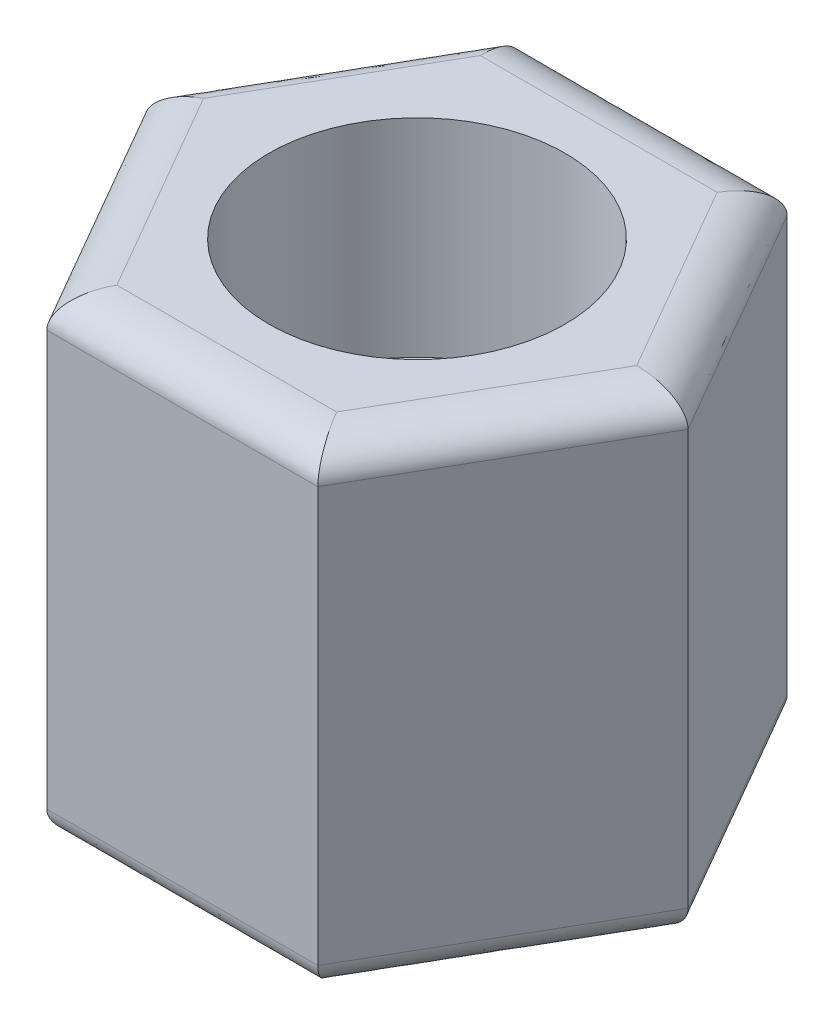
SolidWorks part; units mm, degrees
ref_plane "Front Plane" through (0, 0, 0) normal (0, 0, 1) x (1, 0, 0)
ref_plane "Top Plane" through (0, 0, 0) normal (0, 1, 0) x (1, 0, 0)
ref_plane "Right Plane" through (0, 0, 0) normal (1, 0, 0) x (0, 0, -1)
sketch "Sketch1" plane through (0, 0, 0) normal (0, 1, 0) x (1, 0, 0)
  line L1 (18.3, 0) -> (9.15, 15.8483)
  line L2 (9.15, 15.8483) -> (-9.15, 15.8483)
  line L3 (-9.15, 15.8483) -> (-18.3, 0)
  line L4 (-18.3, 0) -> (-9.15, -15.8483)
  line L5 (-9.15, -15.8483) -> (9.15, -15.8483)
  line L6 (9.15, -15.8483) -> (18.3, 0)
  circle A0 centre (0, 0) radius 18.3 construction
extrude "Boss-Extrude1" add sketch "Sketch1" along normal blind 32
sketch "Sketch2" plane through (0, 32, 0) normal (0, 1, 0) x (1, 0, 0)
  circle A0 centre (0, 0) radius 10
  dimension "D1" = 20
extrude "Cut-Extrude1" cut sketch "Sketch2" against normal blind 14
sketch "Sketch3" plane through (0, 0, 0) normal (0, -1, 0) x (1, 0, 0)
  circle A0 centre (0, 0) radius 10
  dimension "D1" = 20
extrude "Cut-Extrude2" cut sketch "Sketch3" against normal blind 10
fillet "Fillet1" radius 3 6 edges at (-13.725, 0, -7.9241) (-13.725, 0, 7.9241) (0, 0, 15.8483) (13.725, 0, 7.9241) (13.725, 0, -7.9241) (0, 0, -15.8483)
fillet "Fillet2" radius 2 6 edges at (-13.725, 32, -7.9241) (0, 32, -15.8483) (13.725, 32, -7.9241) (13.725, 32, 7.9241) (0, 32, 15.8483) (-13.725, 32, 7.9241)
